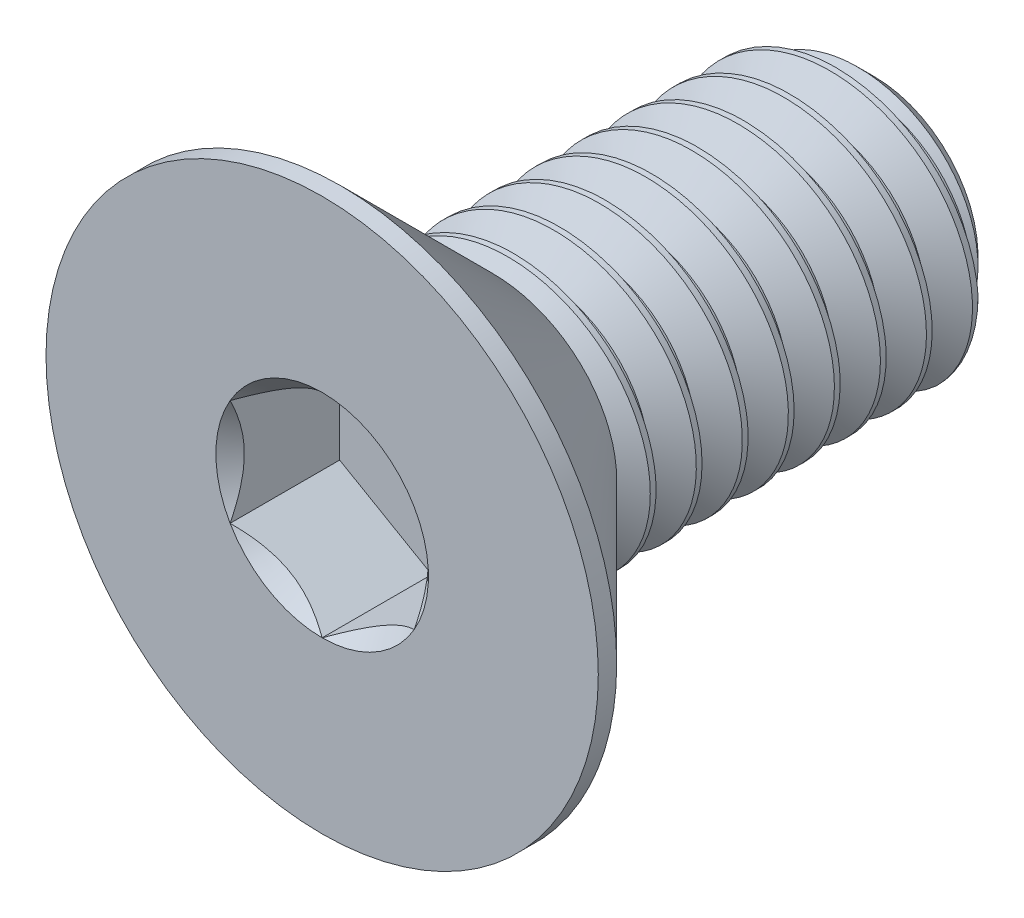
SolidWorks part; units mm, degrees
ref_plane "Front" through (0, 0, 0) normal (0, 0, 1) x (1, 0, 0)
ref_plane "Top" through (0, 0, 0) normal (0, 1, 0) x (1, 0, 0)
ref_plane "Right" through (0, 0, 0) normal (1, 0, 0) x (0, 0, -1)
sketch "Sketch1" plane through (0, 0, 0) normal (1, 0, 0) x (0, 0, -1)
  line L0 (0, 3) -> (0.2, 3) construction
  line L1 (0.2, 3) -> (1.7, 1.5) construction
  line L2 (0, 1.5) -> (6, 1.5)
  line L3 (6, 1.5) -> (6, 0)
  line L4 (6, 0) -> (0, 0)
  line L5 (0, 0) -> (0, 3) construction
  line L6 (0, 3) -> (0, -3) construction
  line L7 (6, 1.5) -> (6, -1.5) construction
  line L8 (0, -3) -> (0.2, -3) construction
  line L9 (0.2, -3) -> (1.7, -1.5) construction
  line L11 (0, 1.5) -> (0, 0)
  line L12 (1.7, 1.5) -> (1.7, 0) construction
revolve "Revolve1" add sketch "Sketch1" angle 360 mid plane about L4
sketch "Sketch3" plane through (0, 0, -6) normal (0, 0, -1) x (-1, 0, 0)
  circle A0 centre (0, 0) radius 1.5
curve "Helix/Spiral1" pitch 0.5 height 6 radius 1.5 centre (0, 0, -6) axis (0, 0, 1) start towards (0, 1, 0)
sketch "Sketch2" plane through (0, 0, 0) normal (1, 0, 0) x (0, 0, -1)
  line L0 (6, 1.5) -> (6.4375, 1.5)
  line L1 (6.4375, 1.5) -> (6.25, 1.1752)
  line L2 (6.25, 1.1752) -> (6.1875, 1.1752)
  line L3 (6.1875, 1.1752) -> (6, 1.5)
  line L4 (6.0938, 1.3376) -> (6.3437, 1.3376) construction
  dimension "D1" = 60
  dimension "D2" = 0.0625
  dimension "D3" = 0.25
chamfer "Chamfer1" distance 0.375 angle 45 1 edges at (0, 1.5, -6)
sweep "Cut-Sweep1" cut profiles "Sketch2" path "Helix/Spiral1" align with end faces yes
sketch "Sketch7" plane through (0, 0, 0) normal (1, 0, 0) x (0, 0, -1)
  line L0 (0, 3) -> (0.2, 3) construction
  line L1 (0.2, 3) -> (1.7, 1.5) construction
  line L2 (0, 3) -> (0.2, 3)
  line L3 (0.2, 3) -> (1.7, 1.5)
  line L4 (1.7, 1.5) -> (1.7, 0) construction
  line L5 (1.7, 1.5) -> (1.7, 0)
  line L7 (0, 0) -> (0, 3) construction
  line L8 (0, 0) -> (0, 3)
  line L9 (0, 0) -> (1.7, 0)
  line L10 (3.3, 0) -> (-3.3, 0) construction
revolve "Revolve2" add sketch "Sketch7" angle 360 mid plane about L9
ref_plane "Plane1" through (0, 0, -1.7) normal (0, 0, 1) x (1, 0, 0)
sketch "Sketch8" plane through (0, 0, -1.7) normal (0, 0, 1) x (1, 0, 0)
  circle A0 centre (0, 0) radius 1.5
extrude "Boss-Extrude1" add sketch "Sketch8" against normal through all draft 45
sketch "Sketch5" plane through (0, 0, 0) normal (0, 0, 1) x (1, 0, 0)
  line L1 (1, -0.5774) -> (1, 0.5774)
  line L2 (1, 0.5774) -> (0, 1.1547)
  line L3 (0, 1.1547) -> (-1, 0.5774)
  line L4 (-1, 0.5774) -> (-1, -0.5774)
  line L5 (-1, -0.5774) -> (0, -1.1547)
  line L6 (0, -1.1547) -> (1, -0.5774)
  circle A0 centre (0, 0) radius 1 construction
  dimension "Hex" = 2
extrude "Cut-Extrude2" cut sketch "Sketch5" against normal blind 1.19
sketch "Sketch6" plane through (0, 0, 0) normal (0, 0, 1) x (1, 0, 0)
  circle A0 centre (0, 0) radius 1.1547
extrude "Cut-Extrude3" cut sketch "Sketch6" against normal blind 1.19 draft 45
sketch "Sketch9" [suppressed] plane through (0, 0, -5.5) normal (0, 0, 1) x (1, 0, 0)
  circle A1 centre (0, 0) radius 5
  circle A2 centre (0, 0) radius 5
  point P0 (0, 5)
  dimension "D1" = 0
extrude "Boss-Extrude2" [suppressed] add sketch "Sketch9" against normal offset from surface (18.5 mm away) 26 up to face at (0, 1.125, -6)
fillet "Fillet1" [suppressed] radius 0.3
sketch "Sketch10" plane through (0, 0, 0) normal (1, 0, 0) x (0, 0, -1)
  line L0 (6, 1.5) -> (6, -1.5) construction
  point P0 (5.25, -1.5)
  dimension "D1" = 0.75
equation "\"D3@Helix/Spiral1\" = \"Lg@Sketch1\""
equation "\"D2@Sketch2\" = \"D4@Helix/Spiral1\" * .125"
equation "\"D3@Sketch2\" = \"D4@Helix/Spiral1\" * .5"
equation "\"D1@Chamfer1\" = \"D4@Helix/Spiral1\" * .75"
equation "\"D1@Cut-Extrude2\" = \"Head Ht@Sketch1\" * .7"
equation "\"D1@Sketch10\" = \"D4@Helix/Spiral1\" * 1.5"
equation "\"D1@Cut-Extrude3\" = \"D1@Cut-Extrude2\""
equation "\"D1@Fillet1\" = \"Dia@Sketch1\" * .1"
